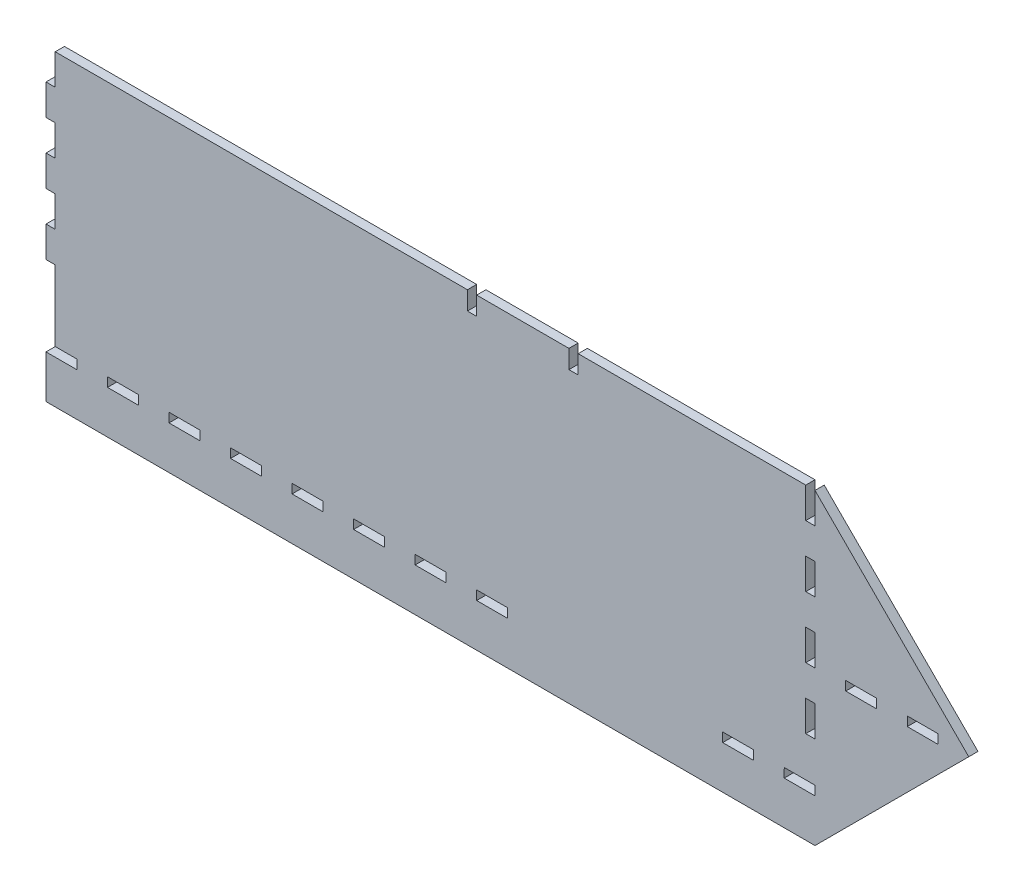
SolidWorks part; units mm, degrees
ref_plane "Front Plane" through (0, 0, 0) normal (0, 0, 1) x (1, 0, 0)
ref_plane "Top Plane" through (0, 0, 0) normal (0, 1, 0) x (1, 0, 0)
ref_plane "Right Plane" through (0, 0, 0) normal (1, 0, 0) x (0, 0, -1)
sketch "Sketch1" plane through (0, 0, 0) normal (0, 0, 1) x (1, 0, 0)
  line L0 (-112.631, -67.7284) -> (-112.631, -53.7284)
  line L1 (134.369, 32.2716) -> (60.379, 32.2716)
  line L2 (-72.631, -50.7284) -> (-62.631, -50.7284)
  line L3 (-62.631, 32.2716) -> (24.379, 32.2716)
  line L4 (137.369, 32.2716) -> (187.369, -17.7284)
  line L5 (187.369, -17.7284) -> (137.369, -67.7284)
  line L6 (137.369, -67.7284) -> (-112.631, -67.7284)
  line L7 (42.379, 32.2716) -> (27.379, 32.2716)
  line L8 (27.379, 32.2716) -> (27.379, 26.2716)
  line L9 (137.369, 32.2716) -> (137.369, -67.7284) construction
  line L10 (137.369, -17.7284) -> (187.369, -17.7284) construction
  line L11 (157.369, -16.2284) -> (147.369, -16.2284)
  line L12 (177.369, -16.2284) -> (167.369, -16.2284)
  line L13 (177.369, -16.2284) -> (177.369, -19.2284)
  line L14 (177.369, -19.2284) -> (167.369, -19.2284)
  line L15 (167.369, -16.2284) -> (167.369, -19.2284)
  line L16 (177.369, -16.2284) -> (167.369, -19.2284) construction
  line L17 (177.369, -19.2284) -> (167.369, -16.2284) construction
  line L18 (157.369, -16.2284) -> (157.369, -19.2284)
  line L19 (157.369, -19.2284) -> (147.369, -19.2284)
  line L20 (147.369, -16.2284) -> (147.369, -19.2284)
  line L21 (137.3812, -50.7284) -> (127.3812, -50.7284)
  line L22 (137.3812, -50.7284) -> (137.3692, -53.7284)
  line L23 (137.3692, -53.7284) -> (127.3692, -53.7284)
  line L24 (127.3812, -50.7284) -> (127.3692, -53.7284)
  line L25 (137.3812, -50.7284) -> (127.3692, -53.7284) construction
  line L26 (137.3692, -53.7284) -> (127.3812, -50.7284) construction
  line L27 (117.3811, -50.7284) -> (107.3787, -50.7284)
  line L28 (117.3811, -50.7284) -> (117.3691, -53.7284)
  line L29 (117.3691, -53.7284) -> (107.3691, -53.7284)
  line L30 (107.3787, -50.7284) -> (107.3691, -53.7284)
  line L31 (117.3811, -50.7284) -> (107.3691, -53.7284) construction
  line L32 (117.3691, -53.7284) -> (107.3787, -50.7284) construction
  line L33 (27.379, 26.2716) -> (24.379, 26.2716)
  line L34 (24.379, 26.2716) -> (24.379, 32.2716)
  line L35 (27.379, 32.2716) -> (57.379, 32.2716)
  line L37 (60.379, 26.2716) -> (60.379, 32.2716)
  line L38 (57.379, 26.2716) -> (60.379, 26.2716)
  line L39 (57.379, 32.2716) -> (57.379, 26.2716)
  line L40 (57.379, 32.2716) -> (42.379, 32.2716)
  line L41 (60.379, 32.2716) -> (134.369, 32.2716)
  line L51 (37.3714, -50.7284) -> (27.369, -50.7284)
  line L52 (37.3714, -50.7284) -> (37.369, -53.7284)
  line L53 (37.369, -53.7284) -> (27.369, -53.7284)
  line L54 (27.369, -50.7284) -> (27.369, -53.7284)
  line L55 (37.3714, -50.7284) -> (27.369, -53.7284) construction
  line L56 (37.369, -53.7284) -> (27.369, -50.7284) construction
  line L57 (17.369, -50.7284) -> (7.369, -50.7284)
  line L58 (17.369, -50.7284) -> (17.369, -53.7284)
  line L59 (17.369, -53.7284) -> (7.369, -53.7284)
  line L60 (7.369, -50.7284) -> (7.369, -53.7284)
  line L61 (17.369, -50.7284) -> (7.369, -53.7284) construction
  line L62 (17.369, -53.7284) -> (7.369, -50.7284) construction
  line L63 (-2.631, -50.7284) -> (-12.631, -50.7284)
  line L64 (-2.631, -50.7284) -> (-2.631, -53.7284)
  line L65 (-2.631, -53.7284) -> (-12.631, -53.7284)
  line L66 (-12.631, -50.7284) -> (-12.631, -53.7284)
  line L67 (-2.631, -50.7284) -> (-12.631, -53.7284) construction
  line L68 (-2.631, -53.7284) -> (-12.631, -50.7284) construction
  line L69 (-22.631, -50.7284) -> (-32.631, -50.7284)
  line L70 (-22.631, -50.7284) -> (-22.631, -53.7284)
  line L71 (-22.631, -53.7284) -> (-32.631, -53.7284)
  line L72 (-32.631, -50.7284) -> (-32.631, -53.7284)
  line L73 (-22.631, -50.7284) -> (-32.631, -53.7284) construction
  line L74 (-22.631, -53.7284) -> (-32.631, -50.7284) construction
  line L75 (-42.631, -50.7284) -> (-52.631, -50.7284)
  line L76 (-42.631, -50.7284) -> (-42.631, -53.7284)
  line L77 (-42.631, -53.7284) -> (-52.631, -53.7284)
  line L78 (-52.631, -50.7284) -> (-52.631, -53.7284)
  line L79 (-42.631, -50.7284) -> (-52.631, -53.7284) construction
  line L80 (-42.631, -53.7284) -> (-52.631, -50.7284) construction
  line L82 (-62.631, -50.7284) -> (-62.631, -53.7284)
  line L83 (-62.631, -53.7284) -> (-72.631, -53.7284)
  line L84 (-72.631, -50.7284) -> (-72.631, -53.7284)
  line L85 (-62.631, -50.7284) -> (-72.631, -53.7284) construction
  line L86 (-62.631, -53.7284) -> (-72.631, -50.7284) construction
  line L87 (137.369, 12.2716) -> (134.369, 12.2716)
  line L88 (-82.631, -50.7284) -> (-82.631, -53.7284)
  line L89 (-82.631, -53.7284) -> (-92.631, -53.7284)
  line L90 (-92.631, -50.7284) -> (-92.631, -53.7284)
  line L91 (-82.631, -50.7284) -> (-92.631, -53.7284) construction
  line L92 (-82.631, -53.7284) -> (-92.631, -50.7284) construction
  line L94 (-102.631, -50.7284) -> (-102.631, -53.7284)
  line L95 (-102.631, -53.7284) -> (-112.631, -53.7284)
  line L97 (-102.631, -50.7284) -> (-112.631, -53.7284) construction
  line L98 (-102.631, -53.7284) -> (-107.631, -52.2284) construction
  line L99 (-62.631, -50.7284) -> (-72.631, -50.7284) [skipped]
  line L100 (-82.631, -50.7284) -> (-92.631, -50.7284) [skipped]
  line L101 (-102.631, -50.7284) -> (-112.631, -50.7284) [skipped]
  line L102 (137.369, 32.2716) -> (137.369, 22.2716)
  line L103 (137.369, 22.2716) -> (134.369, 22.2716)
  line L104 (134.369, 32.2716) -> (134.369, 22.2716)
  line L105 (137.369, 12.2716) -> (137.369, 2.2716)
  line L106 (137.369, 2.2716) -> (134.369, 2.2716)
  line L107 (134.369, 12.2716) -> (134.369, 2.2716)
  line L108 (137.369, -7.7284) -> (134.369, -7.7284)
  line L109 (137.369, -7.7284) -> (137.369, -17.7284)
  line L111 (137.369, -17.7284) -> (134.369, -17.7284)
  line L114 (157.369, -16.2284) -> (147.369, -19.2284) construction
  line L121 (134.369, -7.7284) -> (134.369, -17.7284)
  line L122 (157.369, -19.2284) -> (147.369, -16.2284) construction
  line L124 (-109.631, -50.7284) -> (-102.631, -50.7284)
  line L125 (-112.631, -52.2284) -> (-112.631, -53.3547) [skipped]
  line L126 (-62.631, 32.2716) -> (-109.631, 32.2716)
  line L127 (-112.631, -7.7284) -> (-109.631, -7.7284)
  line L128 (137.369, -27.7284) -> (134.369, -27.7284)
  line L129 (137.369, -27.7284) -> (137.369, -37.7284)
  line L130 (137.369, -37.7284) -> (134.369, -37.7284)
  line L131 (134.369, -27.7284) -> (134.369, -37.7284)
  line L132 (-112.631, 22.2716) -> (-112.631, 12.2716)
  line L133 (-109.631, -17.7284) -> (-112.631, -17.7284)
  line L134 (-112.631, -27.7284) -> (-109.631, -27.7284)
  line L135 (-109.631, -50.7284) -> (-109.631, -27.7284)
  line L136 (-109.631, 2.2716) -> (-112.631, 2.2716)
  line L137 (-112.631, 2.2716) -> (-112.631, -7.7284)
  line L138 (-109.631, 22.2716) -> (-109.631, 32.2716)
  line L139 (-109.631, 22.2716) -> (-112.631, 22.2716)
  line L140 (-112.631, 12.2716) -> (-109.631, 12.2716)
  line L141 (-109.631, -17.7284) -> (-109.631, -7.7284)
  line L142 (-112.631, -17.7284) -> (-112.631, -27.7284)
  line L143 (-109.631, 2.2716) -> (-109.631, 12.2716)
  line L144 (-92.631, -50.7284) -> (-82.631, -50.7284)
  point P5 (172.369, -17.7284)
  point P9 (151.1235, -51.5486)
  point P17 (152.369, -17.7284)
  point P19 (131.1235, -51.6165)
  point P24 (111.1235, -51.6845)
  point P44 (31.1235, -51.9564)
  point P49 (11.1235, -52.0244)
  point P54 (-8.8765, -52.0924)
  point P59 (-28.8765, -52.1604)
  point P64 (-48.8765, -52.2284)
  point P70 (-68.8765, -52.2284)
  point P75 (-88.8765, -52.2284)
  point P80 (-108.8765, -52.2284)
  dimension "D1" = 100
  dimension "D3" = 300
  dimension "D5" = 50
  dimension "D6" = 10
  dimension "D7" = 10
  dimension "D8" = 10
  dimension "D10" = 3
  dimension "D11" = 14
  dimension "D13" = 3
  dimension "D14" = 10
  dimension "D15" = 94.99
  dimension "D17" = 15
  dimension "D18" = 6
  dimension "D19" = 3
  dimension "D21" = 10
  dimension "D22" = 10
  dimension "D23" = 10
  dimension "D24" = 10
  dimension "D25" = 10
  dimension "D26" = 10
  dimension "D9" = 10
  dimension "D27" = 10
  dimension "D28" = 10
  dimension "D29" = 10
  dimension "D30" = 10
  dimension "D31" = 15
  dimension "D38" = 10
  dimension "D39" = 10
  dimension "D40" = 3
  dimension "D41" = 10
  dimension "D20" = 47
  dimension "D42" = 3
  dimension "D12" = 4
  dimension "D16" = 4
extrude "Boss-Extrude1" add sketch "Sketch1" along normal blind 3 contours L94 L95 L0 L6 L5 L4 L3 L82 L83 L84 L88 L89 L90 L24 L21 L22 L23 L30 L27 L28 L29 region at (25.5769, -17.5013, 0)
